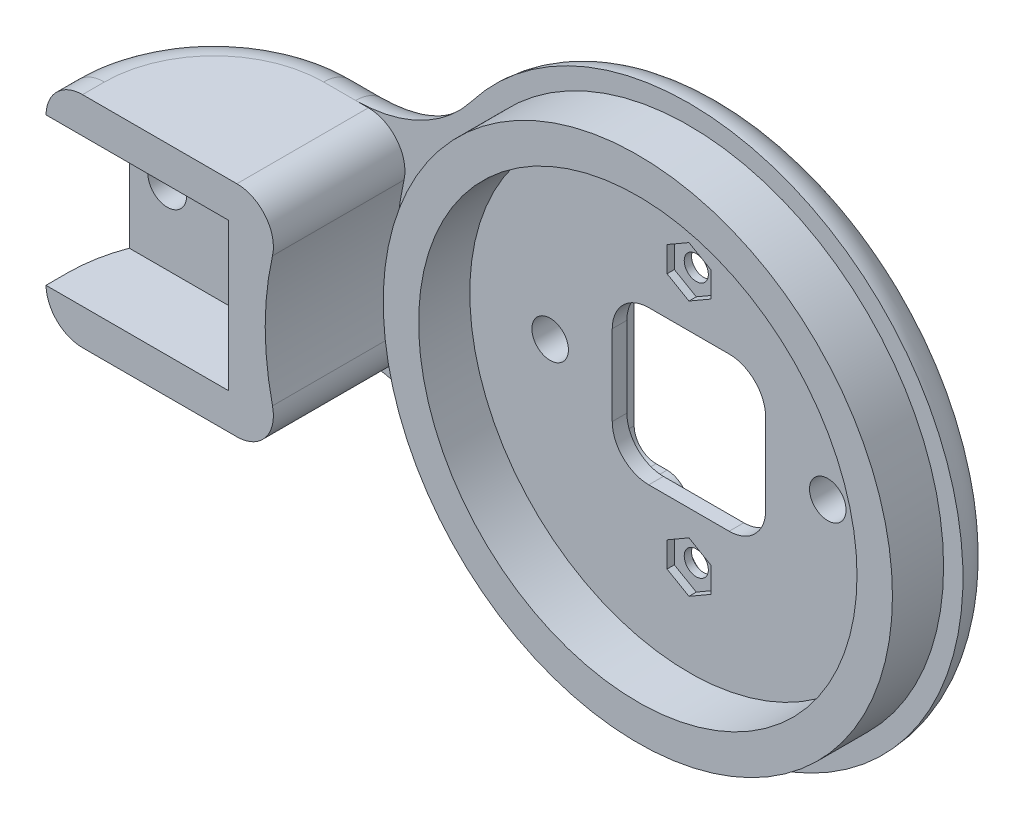
SolidWorks part; units mm, degrees
ref_plane "Plan de face" through (0, 0, 0) normal (0, 0, 1) x (1, 0, 0)
ref_plane "Plan de dessus" through (0, 0, 0) normal (0, 1, 0) x (1, 0, 0)
ref_plane "Plan de droite" through (0, 0, 0) normal (1, 0, 0) x (0, 0, -1)
sketch "Esquisse1" plane through (0, 0, 0) normal (0, 0, 1) x (1, 0, 0)
  line L0 (-1000, 0) -> (49000, 0) construction
  line L1 (-45.6207, 15) -> (-70, 15)
  line L4 (-70, -15) -> (-70, 15)
  line L5 (-45.6207, -15) -> (-70, -15)
  arc A0 (-29.7526, -22.8261) -> (-29.7526, 22.8261) centre (0, 0) ccw
  arc A2 (-45.6207, 15) -> (-29.7526, 22.8261) centre (-45.6207, 35) ccw
  arc A3 (-45.6207, -15) -> (-29.7526, -22.8261) centre (-45.6207, -35) cw
  point P8 (-34.3693, -15)
  point P9 (-70, 0)
  point P13 (-70, 0)
  point P20 (-34.3693, 15)
  dimension "D1" = 75
  dimension "D5" = 20
  dimension "D2" = 15
  dimension "D3" = 70
extrude "Boss.-Extru.1" add sketch "Esquisse1" along normal blind 5
sketch "Esquisse6" plane through (0, 0, 5) normal (0, 0, 1) x (1, 0, 0)
  circle A0 centre (0, 0) radius 34.85
  circle A1 centre (0, 0) radius 30
  dimension "D1" = 69.7
  dimension "D2" = 60
extrude "Boss.-Extru.6" add sketch "Esquisse6" along normal blind 7
sketch "Esquisse8" plane through (0, 0, 5) normal (0, 0, 1) x (1, 0, 0)
  line L1 (-1000, 0) -> (49000, 0) construction
  line L3 (-70, -15) -> (-70, 15)
  line L9 (-70, -15) -> (-43.8748, -15)
  line L10 (-70, 15) -> (-43.8748, 15)
  line L20 (-70, 15) -> (-70, -15) construction
  arc A2 (-38.9998, 8.8889) -> (-38.9998, -8.8889) centre (0, 0) ccw
  arc A3 (-43.8748, 15) -> (-38.9998, 8.8889) centre (-43.8748, 10) cw
  arc A4 (-43.8748, -15) -> (-38.9998, -8.8889) centre (-43.8748, -10) ccw
  point P5 (-70, 0)
  point P15 (-70, 0)
  dimension "D1" = 80
  dimension "D2" = 5
extrude "Boss.-Extru.9" add sketch "Esquisse8" along normal blind 18
sketch "Esquisse21" plane through (0, 0, 0) normal (0, 0, -1) x (-1, 0, 0)
  circle A0 centre (-19, 0) radius 2.5
  circle A1 centre (19, 0) radius 2.5
  point P7 (0, 0)
  dimension "D1" = 5
  dimension "D2" = 19
  dimension "D3" = 2
extrude "Enlèv. mat.-Extru.10" cut sketch "Esquisse21" against normal up to next
sketch "Esquisse22" plane through (0, 0, 0) normal (0, 0, -1) x (-1, 0, 0)
  circle A0 centre (-19, 0) radius 4
  circle A1 centre (19, 0) radius 4
  point P7 (0, 0)
  dimension "D1" = 8
  dimension "D2" = 2
extrude "Enlèv. mat.-Extru.11" cut sketch "Esquisse22" against normal blind 1
fillet "Congé1" radius 20 1 edges at (-70, 0, 0)
fillet "Congé2" radius 5 9 edges at (-47.8104, -15, 0) (-36.7742, -17.0629, 0) (37.5, 0, 0) (-36.7742, 17.0629, 0) (-47.8104, 15, 0) (-64.1421, 15, 5.8579) (-64.1421, -15, 5.8579) (-70, -15, 21.5) (-70, 15, 21.5)
sketch "Esquisse11" plane through (-70, 0, 0) normal (-1, 0, 0) x (0, 0, 1)
  line L0 (23, 10) -> (20, 10) construction
  line L1 (13, 10) -> (33, 10) construction
  line L2 (13, 10) -> (13, -10) construction
  line L3 (13, -10) -> (33, -10) construction
  line L4 (33, 10) -> (33, -10) construction
  line L5 (20, -10) -> (23, -10) construction
  line L6 (0, -10) -> (0, 10) construction
  line L7 (12.9, 10.1) -> (33.1, 10.1)
  line L8 (33.1, 10.1) -> (33.1, -10.1)
  line L9 (12.9, -10.1) -> (33.1, -10.1)
  line L10 (12.9, 10.1) -> (12.9, -10.1)
  dimension "D1" = 13
  dimension "D2" = 20
  dimension "D3" = 0.1
extrude "Enlèv. mat.-Extru.2" cut sketch "Esquisse11" against normal blind 25
sketch "Esquisse12" plane through (0, 0, 12.9) normal (0, 0, 1) x (1, 0, 0)
  line L1 (-45, -10.1) -> (-45, 10.1) construction
  circle A0 centre (-51.5, 0) radius 2.65
  circle A1 centre (-63.5, 0) radius 2.65
  dimension "D1" = 5.3
  dimension "D2" = 6.5
  dimension "D3" = 18.5
extrude "Enlèv. mat.-Extru.3" cut sketch "Esquisse12" against normal through all
sketch "Esquisse13" plane through (0, 0, 12.9) normal (0, 0, 1) x (1, 0, 0)
  circle A0 centre (-51.5, 0) radius 4.5
  circle A1 centre (-63.5, 0) radius 4.5
  dimension "D1" = 9
extrude "Enlèv. mat.-Extru.4" cut sketch "Esquisse13" against normal through all from offset 5 offset against normal yes
sketch "Esquisse14" plane through (0, 0, 5) normal (0, 0, 1) x (1, 0, 0)
  line L6 (-5.5, 10.5) -> (5.5, 10.5)
  line L11 (-1000, 0) -> (49000, 0) construction
  line L16 (-10.5, 5.5) -> (-10.5, -5.5)
  line L17 (-5.5, -10.5) -> (5.5, -10.5)
  line L18 (10.5, 5.5) -> (10.5, -5.5)
  line L19 (-10.5, 10.5) -> (10.5, -10.5) construction
  line L20 (-10.5, -10.5) -> (10.5, 10.5) construction
  arc A8 (-10.5, -5.5) -> (-5.5, -10.5) centre (-5.5, -5.5) ccw
  arc A9 (5.5, -10.5) -> (10.5, -5.5) centre (5.5, -5.5) ccw
  arc A10 (5.5, 10.5) -> (10.5, 5.5) centre (5.5, 5.5) cw
  arc A11 (-5.5, 10.5) -> (-10.5, 5.5) centre (-5.5, 5.5) ccw
  point P0 (0, 0)
  dimension "D2" = 5
  dimension "D1" = 21
extrude "Enlèv. mat.-Extru.5" cut sketch "Esquisse14" against normal blind 2
sketch "Esquisse17" plane through (0, 0, 0) normal (0, 0, -1) x (-1, 0, 0)
  line L6 (0, -1000) -> (0, 49000) construction
  line L17 (-5, -19.5) -> (-5, -15.5)
  line L18 (9.5, -12.5) -> (8, -12.5)
  line L19 (12.5, -9.5) -> (12.5, 9.5)
  line L20 (9.5, 12.5) -> (8, 12.5)
  line L21 (-12.5, -9.5) -> (-12.5, 9.5)
  line L22 (12.5, -12.5) -> (-12.5, 12.5) construction
  line L23 (12.5, 12.5) -> (-12.5, -12.5) construction
  line L24 (2, 22.5) -> (-2, 22.5)
  line L25 (5, 19.5) -> (5, 15.5)
  line L27 (-5, 19.5) -> (-5, 15.5)
  line L28 (5, 22.5) -> (-5, 12.5) construction
  line L29 (5, 12.5) -> (-5, 22.5) construction
  line L30 (-2, -22.5) -> (2, -22.5)
  line L31 (5, -19.5) -> (5, -15.5)
  line L33 (-8, 12.5) -> (-9.5, 12.5)
  line L34 (-8, -12.5) -> (-9.5, -12.5)
  arc A0 (-8, 12.5) -> (-5, 15.5) centre (-8, 15.5) ccw
  arc A1 (-9.5, 12.5) -> (-12.5, 9.5) centre (-9.5, 9.5) ccw
  arc A2 (-9.5, -12.5) -> (-12.5, -9.5) centre (-9.5, -9.5) cw
  arc A3 (-5, -15.5) -> (-8, -12.5) centre (-8, -15.5) ccw
  arc A4 (-5, -19.5) -> (-2, -22.5) centre (-2, -19.5) ccw
  arc A5 (2, -22.5) -> (5, -19.5) centre (2, -19.5) ccw
  arc A6 (5, -15.5) -> (8, -12.5) centre (8, -15.5) cw
  arc A7 (9.5, -12.5) -> (12.5, -9.5) centre (9.5, -9.5) ccw
  arc A8 (12.5, 9.5) -> (9.5, 12.5) centre (9.5, 9.5) ccw
  arc A9 (2, 22.5) -> (5, 19.5) centre (2, 19.5) cw
  arc A10 (5, 15.5) -> (8, 12.5) centre (8, 15.5) ccw
  arc A11 (-2, 22.5) -> (-5, 19.5) centre (-2, 19.5) ccw
  point P0 (0, 0)
  point P6 (0, 17.5)
  point P12 (0, 0)
  point P17 (0, 0)
  dimension "D4" = 3
  dimension "D1" = 25
  dimension "D2" = 10
  dimension "D3" = 2
extrude "Enlèv. mat.-Extru.7" cut sketch "Esquisse17" against normal blind 3
sketch "Esquisse19" plane through (0, 0, 3) normal (0, 0, -1) x (-1, 0, 0)
  line L0 (0, -1000) -> (0, 49000) construction
  line L2 (2, 22.5) -> (-2, 22.5) construction
  circle A2 centre (0, 17.5) radius 1.65
  circle A3 centre (0, -17.5) radius 1.65
  point P11 (0, 0)
  dimension "D1" = 2
  dimension "3.3" = 3.3
  dimension "5" = 5
extrude "Enlèv. mat.-Extru.8" cut sketch "Esquisse19" against normal through all
sketch "Esquisse20" plane through (0, 0, 5) normal (0, 0, 1) x (1, 0, 0)
  line L0 (0, -1000) -> (0, 49000) construction
  line L13 (0, -14.0359) -> (-3, -15.7679)
  line L14 (0, 14.0359) -> (3, 15.7679)
  line L15 (3, 15.7679) -> (3, 19.2321)
  line L16 (3, 19.2321) -> (0, 20.9641)
  line L17 (0, 20.9641) -> (-3, 19.2321)
  line L18 (-3, 19.2321) -> (-3, 15.7679)
  line L19 (-3, 15.7679) -> (0, 14.0359)
  line L20 (-3, -15.7679) -> (-3, -19.2321)
  line L21 (-3, -19.2321) -> (0, -20.9641)
  line L22 (0, -20.9641) -> (3, -19.2321)
  line L23 (3, -19.2321) -> (3, -15.7679)
  line L24 (3, -15.7679) -> (0, -14.0359)
  circle A0 centre (0, 17.5) radius 3 construction
  point P20 (0, 0)
  dimension "D1" = 6
  dimension "D2" = 2
extrude "Enlèv. mat.-Extru.9" cut sketch "Esquisse20" against normal blind 1
